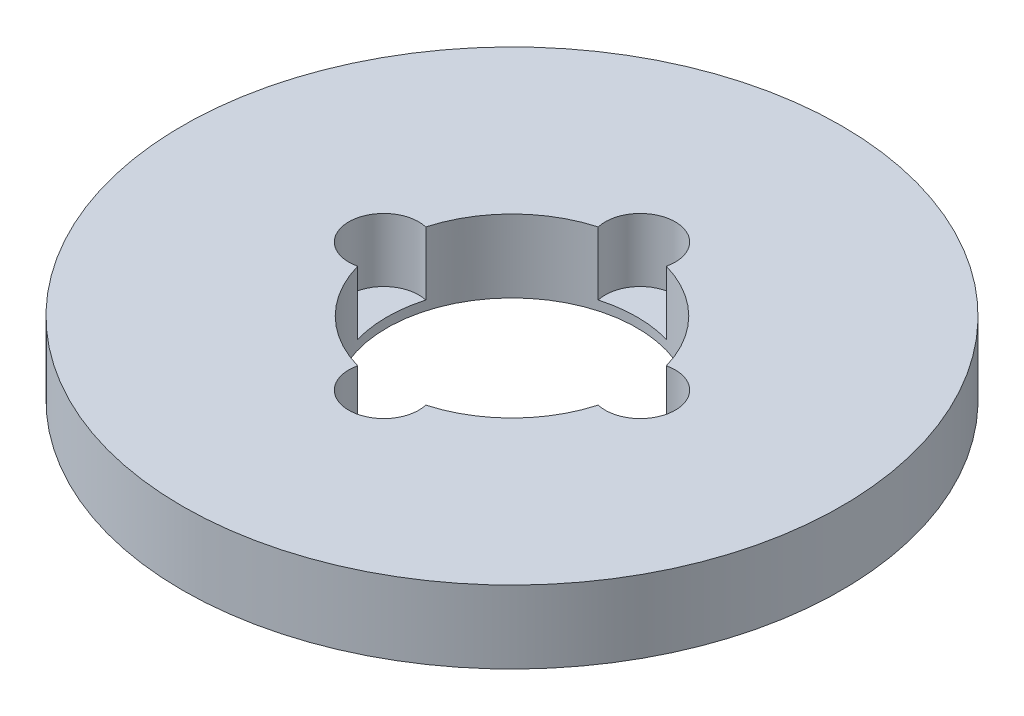
SolidWorks part; units mm, degrees
ref_plane "Front Plane" through (0, 0, 0) normal (0, 0, 1) x (1, 0, 0)
ref_plane "Top Plane" through (0, 0, 0) normal (0, 1, 0) x (1, 0, 0)
ref_plane "Right Plane" through (0, 0, 0) normal (1, 0, 0) x (0, 0, -1)
sketch "Sketch1" plane through (0, 0, 0) normal (0, 1, 0) x (1, 0, 0)
  circle A0 centre (0, 0) radius 72.5
  dimension "FLANGE_OD" = 145
extrude "Boss-Extrude1" add sketch "Sketch1" along normal blind 16
sketch "Sketch2" plane through (0, 0, 0) normal (0, 1, 0) x (1, 0, 0)
  circle A0 centre (0, 0) radius 27.5
  dimension "BORE_D" = 55
extrude "Cut-Extrude1" cut sketch "Sketch2" along normal through all
sketch "Sketch3" plane through (0, 16, 0) normal (0, 1, 0) x (1, 0, 0)
  circle A0 centre (0, 0) radius 28.2119 construction
  circle A1 centre (-28.2119, 0) radius 7.6936
  dimension "BOLT_D" = 15.3871
  dimension "BOLT_PCD" = 56.4239
extrude "Cut-Extrude2" cut sketch "Sketch3" against normal blind 13.9287
pattern_circular "CirPattern1" count 4 over 360 about axis through (0, 0, 0) along (0, 1, 0) of "Cut-Extrude2"
